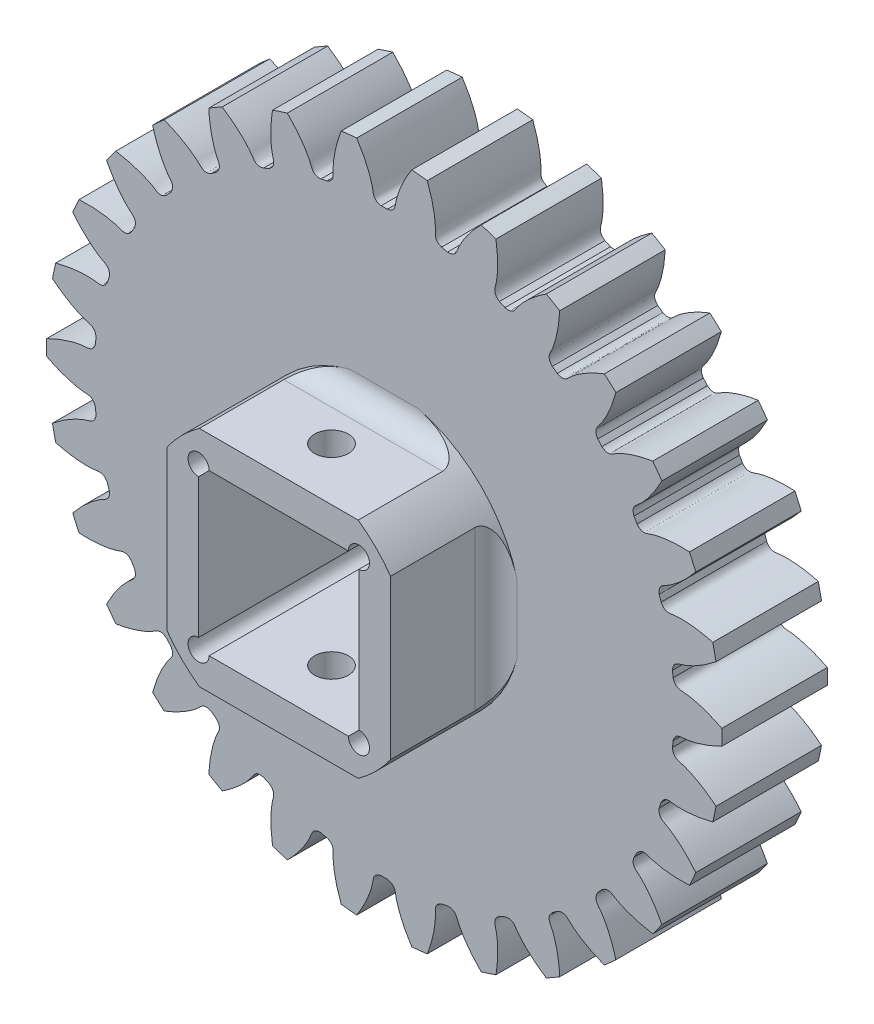
SolidWorks part; units mm, degrees
material "ABS"
ref_plane "前视基准面" through (0, 0, 0) normal (0, 0, 1) x (1, 0, 0)
ref_plane "上视基准面" through (0, 0, 0) normal (0, 1, 0) x (1, 0, 0)
ref_plane "右视基准面" through (0, 0, 0) normal (1, 0, 0) x (0, 0, -1)
other "Configuration Table"
sketch "草图1" plane through (0, 0, 0) normal (0, 0, 1) x (1, 0, 0)
  circle A0 centre (0, 0) radius 32
ref_axis "基准轴1" through (0, 0, -35.2) along (0, 0, 1)
sketch "草图2" plane through (0, 0, 0) normal (0, 0, 1) x (1, 0, 0)
  line L0 (0, 0) -> (0, 32) construction
  circle A0 centre (0, 0) radius 32 construction
  arc A1 (0.2911, 27.4985) -> (-0.2911, 27.4985) centre (0, 0) ccw
  arc A2 (6.7326, 36.3811) -> (-6.7326, 36.3811) centre (0, 0) ccw
  spline S0 degree 3 poles (0.2911, 27.4985) (1.0165, 27.626) (1.0206, 28.0943) (1.118, 28.5772) (1.1399, 28.6763) (1.1665, 28.7858) (1.1981, 28.9058) (1.2353, 29.0359) (1.2783, 29.1761) (1.3276, 29.326) (1.3837, 29.4856) (1.4469, 29.6547) (1.5176, 29.8328) (1.5962, 30.02) (1.6832, 30.2158) (1.7788, 30.4201) (1.8834, 30.6325) (1.9975, 30.8529) (2.1213, 31.0808) (2.2552, 31.3159) (2.3996, 31.5581) (2.5548, 31.8069) (2.7211, 32.0619) (2.8987, 32.323) (3.0881, 32.5896) (3.2895, 32.8614) (3.5032, 33.1381) (3.7295, 33.4192) (3.9685, 33.7044) (4.2207, 33.9933) (4.4861, 34.2854) (4.7651, 34.5803) (5.0578, 34.8776) (5.3645, 35.1769) (5.6854, 35.4777) (6.1378, 35.8852) (6.4907, 36.1841) (6.7326, 36.3811) knots 0 0 0 0 0.115324 0.123413 0.132512 0.142623 0.153745 0.165878 0.179022 0.193177 0.208343 0.22452 0.241708 0.259907 0.279117 0.299338 0.320571 0.342814 0.366068 0.390334 0.41561 0.441898 0.469196 0.497506 0.526827 0.557158 0.588501 0.620855 0.65422 0.688595 0.723982 0.76038 0.797789 0.836209 0.87564 0.916083 1 1 1 1
  spline S1 degree 3 poles (-0.2911, 27.4985) (-1.0165, 27.626) (-1.0206, 28.0943) (-1.118, 28.5772) (-1.1399, 28.6763) (-1.1665, 28.7858) (-1.1981, 28.9058) (-1.2353, 29.0359) (-1.2783, 29.1761) (-1.3276, 29.326) (-1.3837, 29.4856) (-1.4469, 29.6547) (-1.5176, 29.8328) (-1.5962, 30.02) (-1.6832, 30.2158) (-1.7788, 30.4201) (-1.8834, 30.6325) (-1.9975, 30.8529) (-2.1213, 31.0808) (-2.2552, 31.3159) (-2.3996, 31.5581) (-2.5548, 31.8069) (-2.7211, 32.0619) (-2.8987, 32.323) (-3.0881, 32.5896) (-3.2895, 32.8614) (-3.5032, 33.1381) (-3.7295, 33.4192) (-3.9685, 33.7044) (-4.2207, 33.9933) (-4.4861, 34.2854) (-4.7651, 34.5803) (-5.0578, 34.8776) (-5.3645, 35.1769) (-5.6854, 35.4777) (-6.1378, 35.8852) (-6.4907, 36.1841) (-6.7326, 36.3811) knots 0 0 0 0 0.115324 0.123413 0.132512 0.142623 0.153745 0.165878 0.179022 0.193177 0.208343 0.22452 0.241708 0.259907 0.279117 0.299338 0.320571 0.342814 0.366068 0.390334 0.41561 0.441898 0.469196 0.497506 0.526827 0.557158 0.588501 0.620855 0.65422 0.688595 0.723982 0.76038 0.797789 0.836209 0.87564 0.916083 1 1 1 1
extrude "凸台-拉伸1" add sketch "草图1" along normal blind 10
extrude "切除-拉伸1" cut sketch "草图2" along normal through all
pattern_circular "阵列(圆周)1" count 30 every 12 about axis through (0, 0, -35.2) along (0, 0, 1) of "切除-拉伸1"
sketch "草图3" plane through (0, 0, 0) normal (0, 0, 1) x (1, 0, 0)
  circle A0 centre (0, 0) radius 30 construction
  dimension "Dn" = 60
sketch "草图4" plane through (0, 0, 10) normal (0, 0, 1) x (1, 0, 0)
  line L0 (-10.6, -7.526) -> (-10.6, 7.526)
  line L1 (-7.6, -7.6) -> (7.6, -7.6)
  line L2 (-7.6, -7.6) -> (-7.6, 7.6)
  line L3 (-7.6, 7.6) -> (7.6, 7.6)
  line L4 (7.6, -7.6) -> (7.6, 7.6)
  line L5 (-7.6, -7.6) -> (7.6, 7.6) construction
  line L6 (-7.6, 7.6) -> (7.6, -7.6) construction
  line L7 (-7.526, 10.6) -> (7.526, 10.6)
  line L8 (10.6, -7.526) -> (10.6, 7.526)
  line L9 (-7.526, -10.6) -> (7.526, -10.6)
  line L10 (-10.6, 10.6) -> (10.6, 10.6) construction
  line L11 (-10.6, -10.6) -> (-10.6, 10.6) construction
  line L12 (10.6, -10.6) -> (10.6, 10.6) construction
  line L13 (-10.6, -10.6) -> (10.6, -10.6) construction
  arc A0 (-7.526, 10.6) -> (-10.6, 7.526) centre (0, 0) ccw
  arc A1 (10.6, 7.526) -> (7.526, 10.6) centre (0, 0) ccw
  arc A2 (7.526, -10.6) -> (10.6, -7.526) centre (0, 0) ccw
  arc A3 (-10.6, -7.526) -> (-7.526, -10.6) centre (0, 0) ccw
  point P0 (0, 0)
  dimension "D3" = 26
  dimension "D1" = 15.2
  dimension "D2" = 3
extrude "凸台-拉伸2" add sketch "草图4" along normal blind 10
sketch "草图5" plane through (0, 10.6, 0) normal (0, 1, 0) x (1, 0, 0)
  line L0 (0, 0) -> (0, -20) construction
  line L1 (7.526, -20) -> (-7.526, -20) construction
  circle A0 centre (0, -15) radius 1.6
  dimension "D1" = 3.2
  dimension "D2" = 5
extrude "切除-拉伸2" cut sketch "草图5" against normal through all
sketch "草图6" plane through (0, 0, 10) normal (0, 0, 1) x (1, 0, 0)
  line L4 (7.6, -7.6) -> (7.6, 7.6)
  line L5 (7.6, 7.6) -> (-7.6, 7.6)
  line L6 (-7.6, 7.6) -> (-7.6, -7.6)
  line L7 (-7.6, -7.6) -> (7.6, -7.6)
  line L8 (7.6, -7.6) -> (7.6, 7.6)
  line L9 (7.6, 7.6) -> (-7.6, 7.6)
  line L10 (-7.6, 7.6) -> (-7.6, -7.6)
  line L11 (-7.6, -7.6) -> (7.6, -7.6)
  dimension "D1" = 0
extrude "切除-拉伸3" cut sketch "草图6" against normal through all
sketch "草图7" plane through (0, 0, 20) normal (0, 0, 1) x (1, 0, 0)
  circle A0 centre (7.6, 7.6) radius 1
  circle A1 centre (7.6, -7.6) radius 1
  circle A2 centre (-7.6, -7.6) radius 1
  circle A3 centre (-7.6, 7.6) radius 1
  dimension "D1" = 2
  dimension "D2" = 2
  dimension "D3" = 2
  dimension "D4" = 2
extrude "切除-拉伸4" cut sketch "草图7" against normal through all
sketch "草图9" plane through (0, 0, 0) normal (0, 0, -1) x (-1, 0, 0)
  line L0 (6.6, -7.6) -> (-6.6, -7.6) construction
  line L1 (6.6, -7.6) -> (-6.6, -7.6)
  line L2 (-6.6, 7.6) -> (6.6, 7.6) construction
  line L3 (-7.6, -6.6) -> (-7.6, 6.6) construction
  line L4 (7.526, 10.6) -> (-7.526, 10.6)
  line L5 (10.6, -7.526) -> (10.6, 7.526)
  line L6 (-7.526, -10.6) -> (7.526, -10.6)
  line L7 (-10.6, 7.526) -> (-10.6, -7.526)
  line L8 (7.526, 10.6) -> (-7.526, 10.6)
  line L9 (10.6, -7.526) -> (10.6, 7.526)
  line L10 (-7.526, -10.6) -> (7.526, -10.6)
  line L11 (-10.6, 7.526) -> (-10.6, -7.526)
  line L12 (-6.6, 7.6) -> (6.6, 7.6)
  line L13 (-7.6, -6.6) -> (-7.6, 6.6)
  line L14 (7.6, 6.6) -> (7.6, -6.6) construction
  line L15 (7.6, 6.6) -> (7.6, -6.6)
  arc A0 (7.6, 6.6) -> (6.6, 7.6) centre (7.6, 7.6) ccw construction
  arc A1 (-6.6, 7.6) -> (-7.6, 6.6) centre (-7.6, 7.6) ccw construction
  arc A2 (-7.6, -6.6) -> (-6.6, -7.6) centre (-7.6, -7.6) ccw construction
  arc A3 (7.6, 6.6) -> (6.6, 7.6) centre (7.6, 7.6) ccw
  arc A4 (-7.526, 10.6) -> (-10.6, 7.526) centre (0, 0) ccw
  arc A5 (10.6, 7.526) -> (7.526, 10.6) centre (0, 0) ccw
  arc A6 (7.526, -10.6) -> (10.6, -7.526) centre (0, 0) ccw
  arc A7 (-10.6, -7.526) -> (-7.526, -10.6) centre (0, 0) ccw
  arc A8 (-7.526, 10.6) -> (-10.6, 7.526) centre (0, 0) ccw
  arc A9 (10.6, 7.526) -> (7.526, 10.6) centre (0, 0) ccw
  arc A10 (7.526, -10.6) -> (10.6, -7.526) centre (0, 0) ccw
  arc A11 (-10.6, -7.526) -> (-7.526, -10.6) centre (0, 0) ccw
  arc A12 (-6.6, 7.6) -> (-7.6, 6.6) centre (-7.6, 7.6) ccw
  arc A13 (-7.6, -6.6) -> (-6.6, -7.6) centre (-7.6, -7.6) ccw
  arc A14 (6.6, -7.6) -> (7.6, -6.6) centre (7.6, -7.6) ccw construction
  arc A15 (6.6, -7.6) -> (7.6, -6.6) centre (7.6, -7.6) ccw
  dimension "D1" = 0
extrude "凸台-拉伸3" add sketch "草图9" along normal blind 6.5
fillet "圆角1" radius 2 8 edges at (-10.6, 0, 10) (0, 10.6, 10) (10.6, 0, 10) (0, -10.6, 10) (10.6, 0, 0) (0, -10.6, 0) (0, 10.6, 0) (-10.6, 0, 0)
